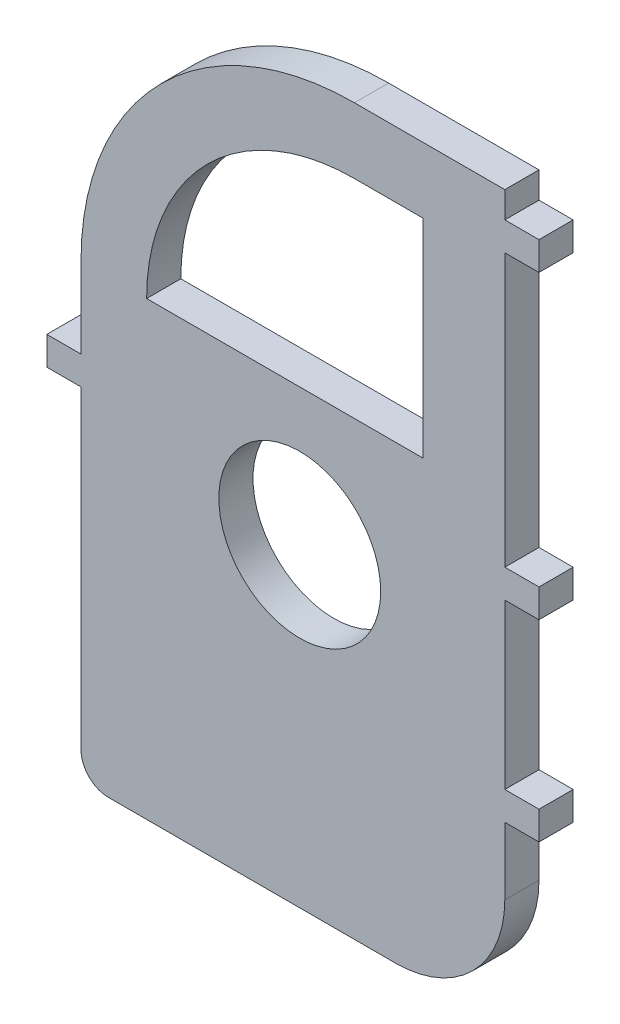
SolidWorks part; units mm, degrees
material "Balsa"
ref_plane "Front Plane" through (0, 0, 0) normal (0, 0, 1) x (1, 0, 0)
ref_plane "Top Plane" through (0, 0, 0) normal (0, 1, 0) x (1, 0, 0)
ref_plane "Right Plane" through (0, 0, 0) normal (1, 0, 0) x (0, 0, -1)
sketch "Sketch1" plane through (0, 0, 0) normal (0, 0, 1) x (1, 0, 0)
  line L0 (0, -1000.1535) -> (0, 48999.8465) construction
  line L2 (-1000, 0) -> (49000, 0) construction
  line L3 (9.525, 16.51) -> (11.1125, 16.51)
  line L4 (2.54, 19.05) -> (9.525, 19.05)
  line L5 (-10.16, 6.35) -> (-10.16, -14.605)
  line L6 (-10.16, -14.605) -> (9.525, -14.605)
  line L7 (9.525, 19.05) -> (9.525, -14.605)
  line L8 (-11.7475, 1.27) -> (-10.16, 1.27)
  line L9 (-11.7475, 1.27) -> (-11.7475, 2.5908)
  line L10 (-11.7475, 2.5908) -> (-10.16, 2.5908)
  line L11 (-10.16, 1.27) -> (-10.16, 2.5908)
  line L12 (9.525, 2.54) -> (11.1125, 2.54)
  line L13 (9.525, 2.54) -> (9.525, 3.8608)
  line L14 (9.525, 3.8608) -> (11.1125, 3.8608)
  line L15 (11.1125, 2.54) -> (11.1125, 3.8608)
  line L16 (9.525, 16.51) -> (9.525, 17.8308)
  line L17 (9.525, 17.8308) -> (11.1125, 17.8308)
  line L18 (11.1125, 16.51) -> (11.1125, 17.8308)
  line L19 (9.525, -5.08) -> (11.1125, -5.08)
  line L20 (9.525, -5.08) -> (9.525, -6.4008)
  line L21 (9.525, -6.4008) -> (11.1125, -6.4008)
  line L22 (11.1125, -5.08) -> (11.1125, -6.4008)
  circle A0 centre (0, 0) radius 3.7592
  arc A3 (2.54, 19.05) -> (-10.16, 6.35) centre (2.54, 6.35) ccw
  dimension "D1" = 7.5184
  dimension "D4" = 14.605
  dimension "D3" = 16.51
  dimension "D5" = 1.5875
  dimension "D9" = 12.7
  dimension "D10" = 1.5875
  dimension "D18" = 1.27
  dimension "D2" = 19.05
  dimension "D6" = 9.525
  dimension "D7" = 1.3208
  dimension "D8" = 19.685
  dimension "D11" = 2.54
  dimension "D12" = 1.3208
  dimension "D13" = 1.3208
  dimension "D14" = 1.5875
  dimension "D19" = 1.5875
  dimension "D20" = 1.3208
  dimension "D21" = 5.08
extrude "Boss-Extrude1" add sketch "Sketch1" along normal blind 1.5875 contours L4 A3 L5 L6 L7 A0 | L10 L9 L8 L5 | L3 L18 L17 L7 | L12 L15 L14 L7 | A3 L5 | L22 L19 L7 L21 region at (10.3187, 17.1704, 0) region at (9.1351, 10.1854, 0) region at (10.3187, 3.2004, 0) region at (10.3187, -5.7404, 0) region at (-10.9538, 1.9304, 0)
fillet "Fillet1" radius 5.08 1 edges at (9.525, -14.605, 0.7937)
fillet "Fillet2" radius 1.27 1 edges at (-10.16, -14.605, 0.7937)
sketch "Sketch2" plane through (0, 0, 1.5875) normal (0, 0, 1) x (1, 0, 0)
  line L0 (-7.112, 6.35) -> (5.715, 6.35)
  line L1 (5.715, 16.002) -> (2.54, 16.002)
  line L2 (5.715, 16.002) -> (5.715, 6.35)
  line L3 (9.525, 16.51) -> (9.525, 3.8608) construction
  arc A2 (2.54, 16.002) -> (-7.112, 6.35) centre (2.54, 6.35) ccw
  arc A3 (2.54, 16.002) -> (-7.112, 6.35) centre (2.54, 6.35) ccw
  dimension "D2" = 3.81
  dimension "D1" = 3.048
extrude "Weight Reduction" cut sketch "Sketch2" against normal up to next
